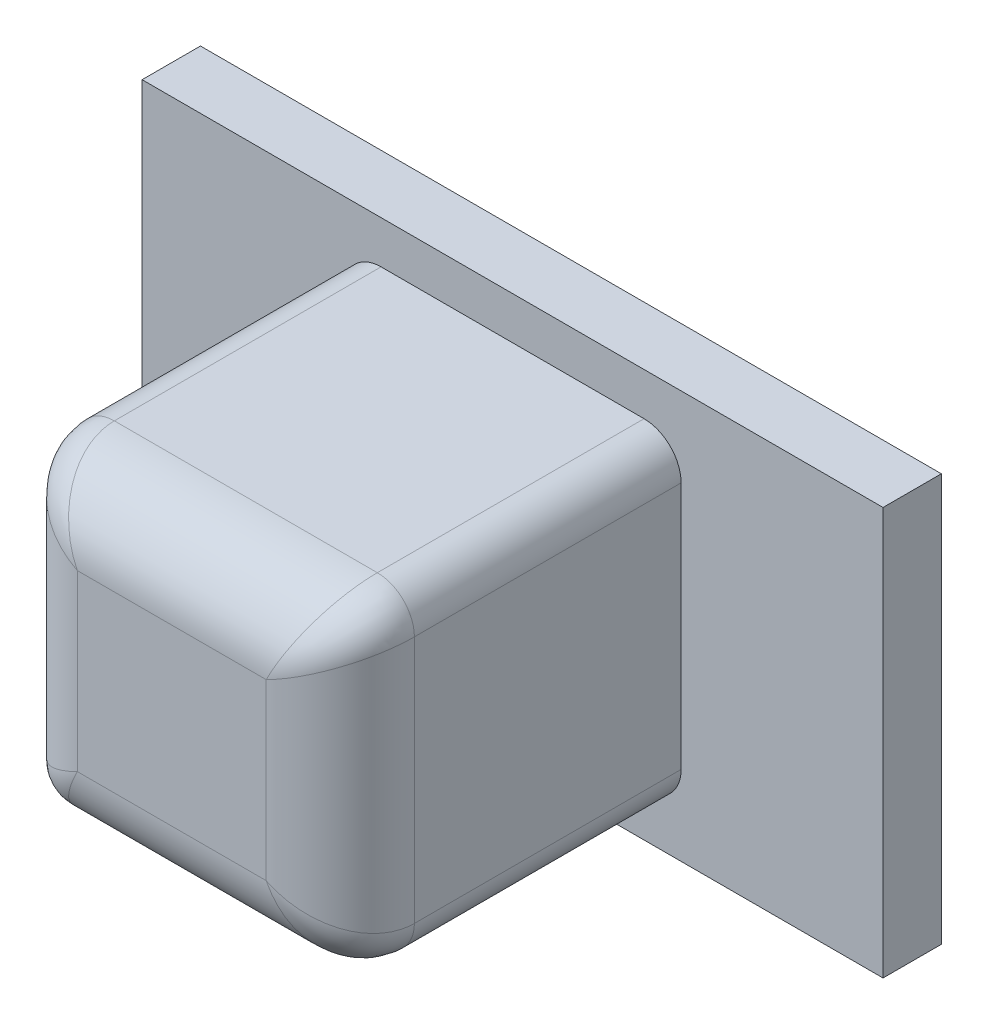
SolidWorks part; units mm, degrees
ref_plane "Front Plane" through (0, 0, 0) normal (0, 0, 1) x (1, 0, 0)
ref_plane "Top Plane" through (0, 0, 0) normal (0, 1, 0) x (1, 0, 0)
ref_plane "Right Plane" through (0, 0, 0) normal (1, 0, 0) x (0, 0, -1)
sketch "Sketch1" plane through (0, 0, 0) normal (0, 0, 1) x (1, 0, 0)
  line L0 (-2.889, 2.762) -> (2.889, 2.762)
  line L1 (-0.889, 0.762) -> (0.889, 0.762)
  line L2 (-0.889, 0.762) -> (-0.889, -0.762)
  line L3 (-0.889, -0.762) -> (0.889, -0.762)
  line L4 (0.889, 0.762) -> (0.889, -0.762)
  line L5 (-0.889, 0.762) -> (0.889, -0.762) construction
  line L6 (-0.889, -0.762) -> (0.889, 0.762) construction
  line L7 (2.889, 2.762) -> (2.889, -2.762)
  line L8 (-2.889, -2.762) -> (2.889, -2.762)
  line L9 (-2.889, 2.762) -> (-2.889, -2.762)
  point P0 (0, 0)
  point P5 (0, 0)
  dimension "D1" = 1.524
  dimension "D2" = 1.778
  dimension "D3" = 2
extrude "Boss-Extrude1" add sketch "Sketch1" along normal blind 5.842
sketch "Sketch2" plane through (0, 0, 5.842) normal (0, 0, 1) x (1, 0, 0)
  line L8 (-2.889, 2.762) -> (-2.889, -2.762)
  line L9 (-2.889, -2.762) -> (2.889, -2.762)
  line L10 (2.889, -2.762) -> (2.889, 2.762)
  line L11 (2.889, 2.762) -> (-2.889, 2.762)
  line L12 (-2.889, 2.762) -> (-2.889, -2.762)
  line L13 (-2.889, -2.762) -> (2.889, -2.762)
  line L14 (2.889, -2.762) -> (2.889, 2.762)
  line L15 (2.889, 2.762) -> (-2.889, 2.762)
  dimension "D1" = 0
extrude "Boss-Extrude2" add sketch "Sketch2" against normal blind 2.54
sketch "Sketch3" plane through (0, 0, 0) normal (0, 0, 1) x (1, 0, 0)
  line L1 (-6.35, 3.4925) -> (6.35, 3.4925)
  line L2 (-6.35, 3.4925) -> (-6.35, -3.4925)
  line L3 (-6.35, -3.4925) -> (6.35, -3.4925)
  line L4 (6.35, 3.4925) -> (6.35, -3.4925)
  line L5 (-6.35, 3.4925) -> (6.35, -3.4925) construction
  line L6 (-6.35, -3.4925) -> (6.35, 3.4925) construction
  line L14 (0.889, -0.762) -> (0.889, 0.762)
  line L15 (-0.889, -0.762) -> (0.889, -0.762)
  line L16 (-0.889, 0.762) -> (-0.889, -0.762)
  line L17 (0.889, 0.762) -> (-0.889, 0.762)
  line L18 (0.889, -0.762) -> (0.889, 0.762)
  line L19 (-0.889, -0.762) -> (0.889, -0.762)
  line L20 (-0.889, 0.762) -> (-0.889, -0.762)
  line L21 (0.889, 0.762) -> (-0.889, 0.762)
  point P0 (0, 0)
  dimension "D1" = 12.7
  dimension "D2" = 6.985
  dimension "D3" = 0
extrude "Boss-Extrude3" add sketch "Sketch3" against normal blind 1
fillet "Fillet1" radius 0.635 4 edges at (2.889, -2.762, 2.921) (-2.889, -2.762, 2.921) (-2.889, 2.762, 2.921) (2.889, 2.762, 2.921)
fillet "Fillet2" radius 1.27 8 edges at (-2.703, -2.576, 5.842) (-2.889, 0, 5.842) (-2.703, 2.576, 5.842) (0, 2.762, 5.842) (2.703, 2.576, 5.842) (2.889, 0, 5.842) (2.703, -2.576, 5.842) (0, -2.762, 5.842)
